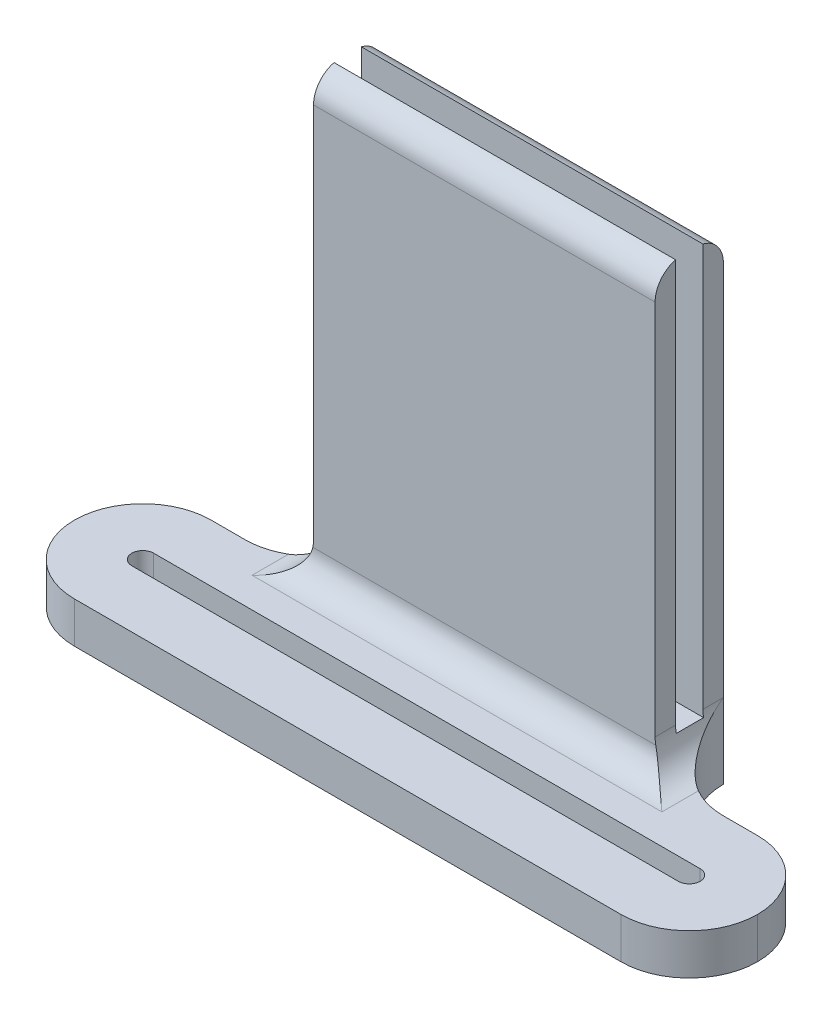
SolidWorks part; units mm, degrees
ref_plane "Front Plane" through (0, 0, 0) normal (0, 0, 1) x (1, 0, 0)
ref_plane "Top Plane" through (0, 0, 0) normal (0, 1, 0) x (1, 0, 0)
ref_plane "Right Plane" through (0, 0, 0) normal (1, 0, 0) x (0, 0, -1)
sketch "Sketch1" plane through (0, 0, 0) normal (0, 1, 0) x (1, 0, 0)
  line L1 (-25, -5) -> (25, -5)
  line L2 (-25, -5) -> (-25, 5)
  line L3 (-25, 5) -> (25, 5)
  line L4 (25, -5) -> (25, 5)
  line L5 (-25, -5) -> (25, 5) construction
  line L6 (-25, 5) -> (25, -5) construction
  point P0 (0, 0)
  dimension "D1" = 10
  dimension "D2" = 50
extrude "Boss-Extrude1" add sketch "Sketch1" along normal blind 70
sketch "Sketch2" plane through (0, 70, 0) normal (0, 1, 0) x (1, 0, 0)
  line L0 (25, -5) -> (25, 5) construction
  line L1 (-25, -2) -> (25, -2)
  line L2 (-25, -2) -> (-25, 2)
  line L3 (-25, 2) -> (25, 2)
  line L4 (25, -2) -> (25, 2)
  line L5 (-25, -2) -> (25, 2) construction
  line L6 (-25, 2) -> (25, -2) construction
  point P0 (0, 0)
  dimension "D1" = 4
extrude "Cut-Extrude1" cut sketch "Sketch2" against normal blind 60
sketch "Sketch3" plane through (0, 0, 5) normal (0, 0, 1) x (1, 0, 0)
  line L1 (-50, 0) -> (50, 0)
  line L2 (-50, 0) -> (-50, 6)
  line L3 (-50, 6) -> (50, 6)
  line L4 (50, 0) -> (50, 6)
  line L5 (25, 0) -> (-25, 0) construction
  point P4 (0, 6)
  dimension "D1" = 6
  dimension "D2" = 100
extrude "Boss-Extrude2" add sketch "Sketch3" along normal blind 20
fillet "Fillet1" radius 10 4 edges at (50, 3, 25) (-50, 3, 25) (-50, 3, 5) (50, 3, 5)
fillet "Fillet2" radius 10 2 edges at (-25, 3, 5) (25, 3, 5)
fillet "Fillet3" radius 5 2 edges at (-25, 6, 0) (25, 6, 0)
sketch "Sketch4" plane through (0, 6, 0) normal (0, 1, 0) x (1, 0, 0)
  line L0 (-40, -15) -> (40, -15) construction
  line L1 (-40, -13.4) -> (40, -13.4)
  line L2 (-40, -16.6) -> (40, -16.6)
  arc A0 (-40, -13.4) -> (-40, -16.6) centre (-40, -15) ccw
  arc A1 (40, -16.6) -> (40, -13.4) centre (40, -15) ccw
  arc A2 (-40, -5) -> (-50, -15) centre (-40, -15) ccw construction
  arc A3 (50, -15) -> (40, -5) centre (40, -15) ccw construction
  point P2 (0, -15)
  dimension "D1" = 3.2
extrude "Cut-Extrude2" cut sketch "Sketch4" against normal through all
fillet "Fillet4" radius 4 2 edges at (0, 70, 5) (0, 70, -5)
fillet "Fillet5" radius 4 1 edges at (0, 6, 5)
